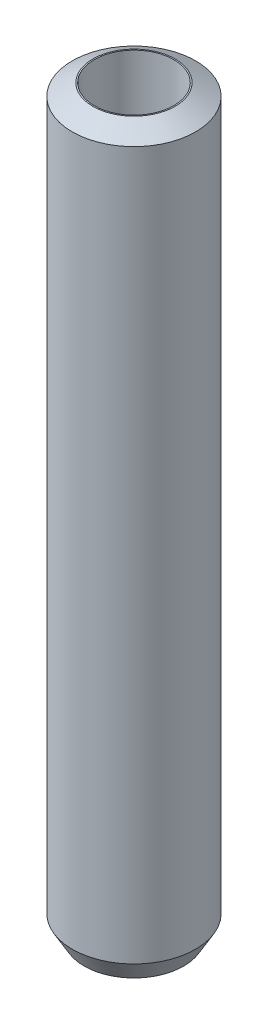
SolidWorks part; units mm, degrees
ref_plane "Front Plane" through (0, 0, 0) normal (0, 0, 1) x (1, 0, 0)
ref_plane "Top Plane" through (0, 0, 0) normal (0, 1, 0) x (1, 0, 0)
ref_plane "Right Plane" through (0, 0, 0) normal (1, 0, 0) x (0, 0, -1)
sketch "Sketch1" plane through (0, 0, 0) normal (0, 1, 0) x (1, 0, 0)
  circle A0 centre (0, 0) radius 10
  dimension "SHAFT_OD" = 20
extrude "Boss-Extrude1" add sketch "Sketch1" along normal blind 120.0692
sketch "Sketch2" plane through (0, 0, 0) normal (0, 1, 0) x (1, 0, 0)
  circle A0 centre (0, 0) radius 6.4621
  dimension "BORE_D" = 12.9243
extrude "Cut-Extrude1" cut sketch "Sketch2" along normal through all
chamfer "Chamfer1" distance 1.9223 angle 60 2 edges at (0, 120.0692, 10) (0, 0, 10) first distance on face at (0, 120.0692, 10) first distance on face at (0, 0, 6.4621)
